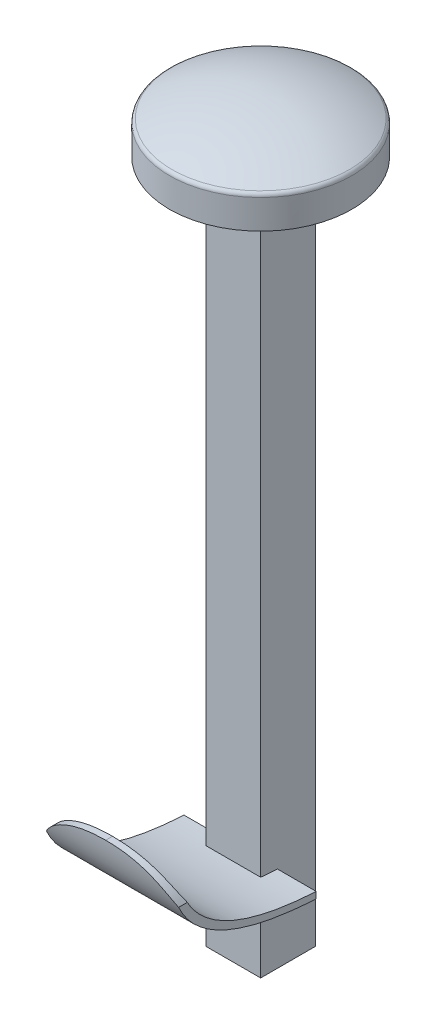
SolidWorks part; units mm, degrees
ref_plane "Front Plane" through (0, 0, 0) normal (0, 0, 1) x (1, 0, 0)
ref_plane "Top Plane" through (0, 0, 0) normal (0, 1, 0) x (1, 0, 0)
ref_plane "Right Plane" through (0, 0, 0) normal (1, 0, 0) x (0, 0, -1)
sketch "Sketch1" plane through (0, 0, 0) normal (0, 1, 0) x (1, 0, 0)
  line L1 (-0.6, -0.6) -> (0.6, -0.6)
  line L2 (-0.6, -0.6) -> (-0.6, 0.6)
  line L3 (-0.6, 0.6) -> (0.6, 0.6)
  line L4 (0.6, -0.6) -> (0.6, 0.6)
  line L5 (-0.6, -0.6) -> (0.6, 0.6) construction
  line L6 (-0.6, 0.6) -> (0.6, -0.6) construction
  point P5 (0, 0)
  dimension "D1" = 1.2
  dimension "D2" = 1.2
extrude "Boss-Extrude1" add sketch "Sketch1" against normal blind 15
sketch "Sketch2" plane through (0, 0, 0) normal (0, 1, 0) x (1, 0, 0)
  circle A0 centre (0, 0) radius 2
  dimension "D1" = 4
extrude "Boss-Extrude2" add sketch "Sketch2" along normal blind 0.7
dome "Dome1" faces to dome 1 distance 0.5 reverse direction no elliptical dome no face at (0, 0.7, 2) parameters "D1"=0.5
fillet "Fillet1" radius 0.1 1 edges at (0, 0.7, 2)
sketch "Sketch4" plane through (0, 0, 0) normal (1, 0, 0) x (0, 0, -1)
  line L0 (-3.4004, -11.2823) -> (-3.2504, -11.2823)
  line L4 (-0.2317, -13.1148) -> (-0.2317, -13.2544)
  spline S0 degree 2 poles (-0.2317, -13.2544) (-3.2797, -13.09) (-3.4004, -11.2823) knots 0 0 0 1 1 1
  spline S1 degree 2 poles (-3.2504, -11.2823) (-3.0587, -12.9556) (-0.2317, -13.1148) knots 0 0 0 1 1 1
  dimension "D2" = 0.15
extrude "Boss-Extrude4" add sketch "Sketch4" along normal mid plane 2.9
ref_plane "Plane1" through (0, 0, 3.6) normal (0, 0, 1) x (1, 0, 0)
sketch "Sketch5" plane through (0, 0, 3.6) normal (0, 0, 1) x (1, 0, 0)
  line L0 (0, -8.4886) -> (0, -17.4575) construction
  line L1 (-1.0383, -11.2823) -> (1.0383, -11.2823) construction
  line L2 (-1.6358, -12.2898) -> (-1.9221, -12.2898)
  line L3 (-1.9221, -12.2898) -> (-2.1588, -10.5237)
  line L4 (-2.1588, -10.5237) -> (2.2121, -10.5237)
  line L5 (2.2121, -10.5237) -> (1.9686, -12.3729)
  line L6 (1.9686, -12.3729) -> (1.6358, -12.2898)
  spline S0 degree 2 poles (0, -11.2823) (-1.2978, -11.2823) (-1.6358, -12.2898) knots 0 0 0 1 1 1
  spline S1 degree 2 poles (0, -11.2823) (1.2978, -11.2823) (1.6358, -12.2898) knots 0 0 0 1 1 1
extrude "Cut-Extrude1" cut sketch "Sketch5" against normal blind 1
